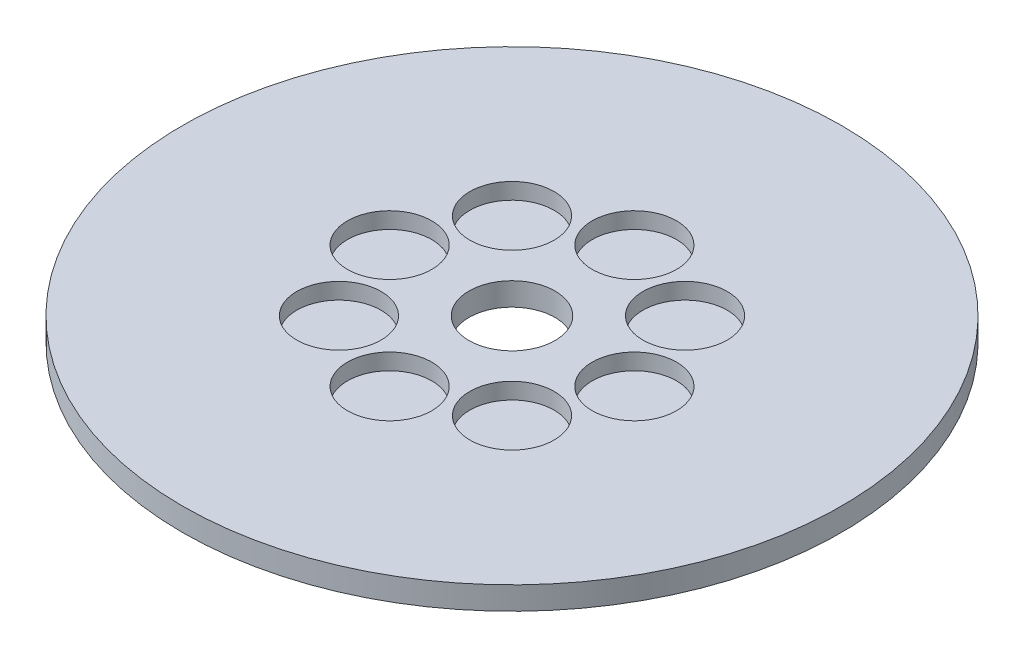
SolidWorks part; units mm, degrees
ref_plane "Front Plane" through (0, 0, 0) normal (0, 0, 1) x (1, 0, 0)
ref_plane "Top Plane" through (0, 0, 0) normal (0, 1, 0) x (1, 0, 0)
ref_plane "Right Plane" through (0, 0, 0) normal (1, 0, 0) x (0, 0, -1)
sketch "Sketch1" plane through (0, 0, 0) normal (0, 1, 0) x (1, 0, 0)
  circle A0 centre (0, 0) radius 57.5
  dimension "FLANGE_OD" = 115
extrude "Boss-Extrude1" add sketch "Sketch1" along normal blind 4
sketch "Sketch2" plane through (0, 0, 0) normal (0, 1, 0) x (1, 0, 0)
  circle A0 centre (0, 0) radius 7.5
  dimension "BORE_D" = 15
extrude "Cut-Extrude1" cut sketch "Sketch2" along normal through all
sketch "Sketch3" plane through (0, 4, 0) normal (0, 1, 0) x (1, 0, 0)
  circle A0 centre (0, 0) radius 21.3513 construction
  circle A1 centre (-21.3513, 0) radius 7.3565
  dimension "BOLT_D" = 14.7131
  dimension "BOLT_PCD" = 42.7025
extrude "Cut-Extrude2" cut sketch "Sketch3" against normal blind 2.837
pattern_circular "CirPattern1" count 8 over 360 about axis through (0, 0, 0) along (0, 1, 0) of "Cut-Extrude2"
